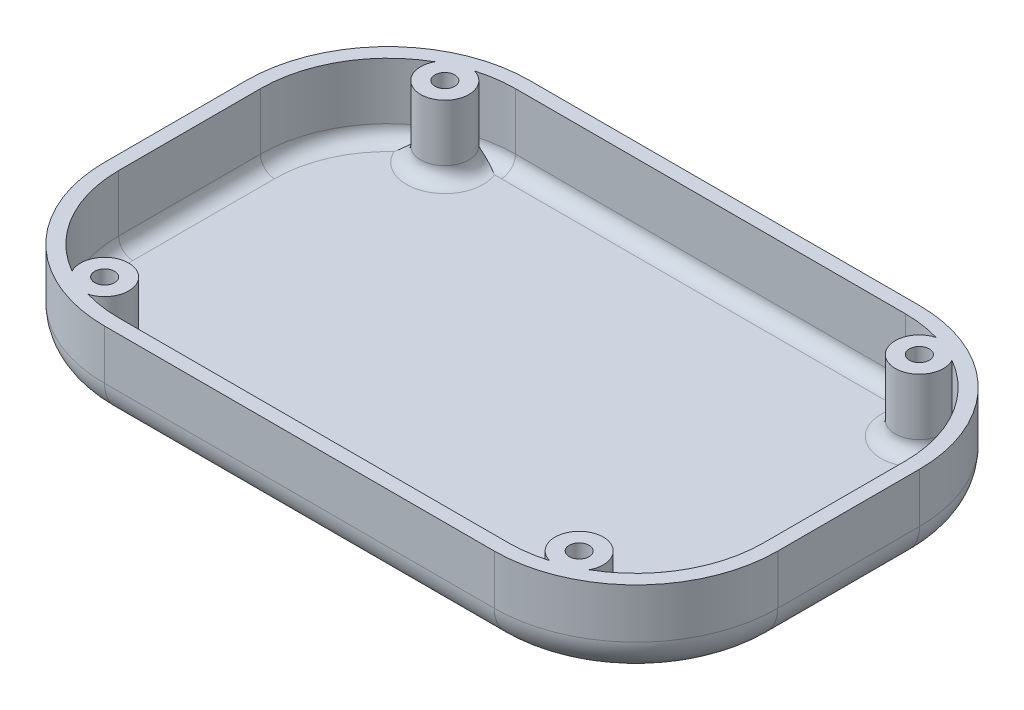
SolidWorks part; units mm, degrees
ref_plane "Front Plane" through (0, 0, 0) normal (0, 0, 1) x (1, 0, 0)
ref_plane "Top Plane" through (0, 0, 0) normal (0, 1, 0) x (1, 0, 0)
ref_plane "Right Plane" through (0, 0, 0) normal (1, 0, 0) x (0, 0, -1)
sketch "Sketch1" plane through (0, 0, 0) normal (0, 1, 0) x (1, 0, 0)
  line L0 (47.5, -7.5) -> (47.5, 7.5)
  line L1 (27.5, 26.9174) -> (27.5, 21.5)
  line L2 (32.5, 16.5) -> (35.5, 16.5)
  line L3 (38.5, 13.5) -> (38.5, 7.5)
  line L4 (38.5, 7.5) -> (47.5, 7.5)
  line L5 (47.5, 7.5) -> (47.5, 10)
  line L6 (27.5, 30) -> (-27.5, 30)
  line L7 (-47.5, 10) -> (-47.5, -10)
  line L8 (-27.5, -30) -> (27.5, -30)
  line L9 (47.5, -10) -> (47.5, -7.5)
  line L10 (47.5, -7.5) -> (38.5, -7.5)
  line L11 (38.5, -7.5) -> (38.5, -13.5)
  line L12 (35.5, -16.5) -> (33.5, -16.5)
  line L13 (28.5, -21.5) -> (28.5, -27.5)
  line L14 (28.5, -27.5) -> (-29.8564, -27.5)
  line L15 (-29.8564, -27.5) -> (-29.8564, -21.5)
  line L16 (-34.8564, -16.5) -> (-35.5, -16.5)
  line L17 (-38.5, -13.5) -> (-44.1621, -13.5)
  line L18 (-44.1621, -13.5) -> (-44.1621, 13.5)
  line L19 (-44.1621, 13.5) -> (-38.5, 13.5)
  line L20 (-35.5, 16.5) -> (-32.5, 16.5)
  line L21 (-27.5, 21.5) -> (-27.5, 26.9174)
  line L22 (-27.5, 26.9174) -> (27.5, 26.9174)
  line L23 (27.5, 28) -> (-27.5, 28)
  line L24 (-45.5, 10) -> (-45.5, -10)
  line L25 (-27.5, -28) -> (27.5, -28)
  line L26 (45.5, -10) -> (45.5, -7.5)
  line L27 (45.5, -7.5) -> (45.5, 7.5)
  line L28 (45.5, 7.5) -> (45.5, 10)
  circle A0 centre (-33.4806, 24) radius 1.4
  circle A1 centre (33.4806, -24) radius 1.4
  circle A2 centre (-33.4806, -24) radius 1.4
  circle A3 centre (33.4806, 24) radius 1.4
  arc A4 (27.5, 21.5) -> (32.5, 16.5) centre (32.5, 21.5) ccw
  arc A5 (38.5, 13.5) -> (35.5, 16.5) centre (35.5, 13.5) ccw
  arc A6 (47.5, 10) -> (27.5, 30) centre (27.5, 10) ccw
  arc A7 (-27.5, 30) -> (-47.5, 10) centre (-27.5, 10) ccw
  arc A8 (-47.5, -10) -> (-27.5, -30) centre (-27.5, -10) ccw
  arc A9 (27.5, -30) -> (47.5, -10) centre (27.5, -10) ccw
  arc A10 (35.5, -16.5) -> (38.5, -13.5) centre (35.5, -13.5) ccw
  arc A11 (33.5, -16.5) -> (28.5, -21.5) centre (33.5, -21.5) ccw
  arc A12 (-29.8564, -21.5) -> (-34.8564, -16.5) centre (-34.8564, -21.5) ccw
  arc A13 (-38.5, -13.5) -> (-35.5, -16.5) centre (-35.5, -13.5) ccw
  arc A14 (-35.5, 16.5) -> (-38.5, 13.5) centre (-35.5, 13.5) ccw
  arc A15 (-32.5, 16.5) -> (-27.5, 21.5) centre (-32.5, 21.5) ccw
  arc A16 (-27.5, 28) -> (-45.5, 10) centre (-27.5, 10) ccw
  arc A17 (-45.5, -10) -> (-27.5, -28) centre (-27.5, -10) ccw
  arc A18 (27.5, -28) -> (45.5, -10) centre (27.5, -10) ccw
  arc A19 (45.5, 10) -> (27.5, 28) centre (27.5, 10) ccw
  circle A20 centre (-33.4806, 24) radius 3.4
  circle A21 centre (33.4806, 24) radius 3.4
  circle A22 centre (33.4806, -24) radius 3.4
  circle A23 centre (-33.4806, -24) radius 3.4
  dimension "D5" = 2.8
  dimension "D6" = 2.8
  dimension "D7" = 2.8
  dimension "D8" = 2.8
  dimension "D1" = 95
  dimension "D2" = 60
  dimension "D3" = 2
  dimension "D4" = 2
extrude "Boss-Extrude1" add sketch "Sketch1" against normal blind 2 contours A23 A17 L24 A16 A20 L23 A19 A21 L28 L4 L5 A6 L6 A7 L7 A8 L8 A9 L9 L10 L26 A18 A22 L25 | A17 A23 | A17 A23 A2 | A23 A17 L25 A18 A22 L26 L10 L11 A10 L12 A11 L13 L14 L15 A12 L16 A13 L17 L18 L19 A14 L20 A15 L21 L22 L1 A4 L2 A5 L3 L4 L28 A19 A21 L23 A16 A20 L24 | A2 | A15 L20 A14 L19 L18 L17 A13 L16 A12 L15 L14 L13 A11 L12 A10 L11 L10 L27 L4 L3 A5 L2 A4 L1 L22 L21 | A18 A22 A1 | A18 A22 | L27 L10 L0 L4 | A19 A21 A3 | A19 A21 | A3 | A1 | A16 A20 A0 | A16 A20 | A0 region at (46.5, 0, 0) region at (46.3764, 0, 8.75) region at (44.4315, 0, 8.75) region at (-0.5838, 0, 0.4182) region at (34.6601, 0, 26.7612) region at (34.5337, 0, 26.4653) region at (36.6867, 0, -24.8012) region at (34.6601, 0, -26.7612) region at (-34.6601, 0, 26.7612) region at (-34.5337, 0, 26.4653) region at (-30.847, 0, -25.9963) region at (-34.6601, 0, -26.7612) region at (-33.4806, 0, -24) region at (33.4806, 0, 24) region at (-33.4806, 0, 24) region at (33.4806, 0, -24)
extrude "Boss-Extrude2" add sketch "Sketch1<3>" along normal blind 10 contours A23 A17 L24 A16 A20 L23 A19 A21 L28 L4 L5 A6 L6 A7 L7 A8 L8 A9 L9 L10 L26 A18 A22 L25 | A17 A23 A2 | A16 A20 A0 | A19 A21 A3 | A18 A22 A1 | L27 L10 L0 L4 | A16 A20 | A17 A23 | A18 A22 | A19 A21 region at (46.5, 0, 0) region at (46.3764, 0, 8.75) region at (34.6601, 0, 26.7612) region at (34.5337, 0, 26.4653) region at (36.6867, 0, -24.8012) region at (34.6601, 0, -26.7612) region at (-34.6601, 0, 26.7612) region at (-34.5337, 0, 26.4653) region at (-30.847, 0, -25.9963) region at (-34.6601, 0, -26.7612)
sketch "Sketch1<3>" plane through (0, 0, 0) normal (0, 1, 0) x (1, 0, 0) same geometry as "Sketch1"
fillet "Fillet1" radius 5 8 edges at (47.5, -2, 0) (41.6421, -2, -24.1421) (0, -2, -30) (-41.6421, -2, -24.1421) (-47.5, -2, 0) (-41.6421, -2, 24.1421) (0, -2, 30) (41.6421, -2, 24.1421)
fillet "Fillet2" radius 2 16 edges at (45.5, 0, 0) (43.0829, 0, 19.0096) (32.1449, 0, 20.8733) (30.0569, 0, 27.8175) (0, 0, 28) (-30.0569, 0, 27.8175) (-32.1449, 0, 20.8733) (-43.0829, 0, 19.0096) (-45.5, 0, 0) (-43.0829, 0, -19.0096) (-32.1449, 0, -20.8733) (-30.0569, 0, -27.8175) (0, 0, -28) (30.0569, 0, -27.8175) (32.1449, 0, -20.8733) (43.0829, 0, -19.0096)
